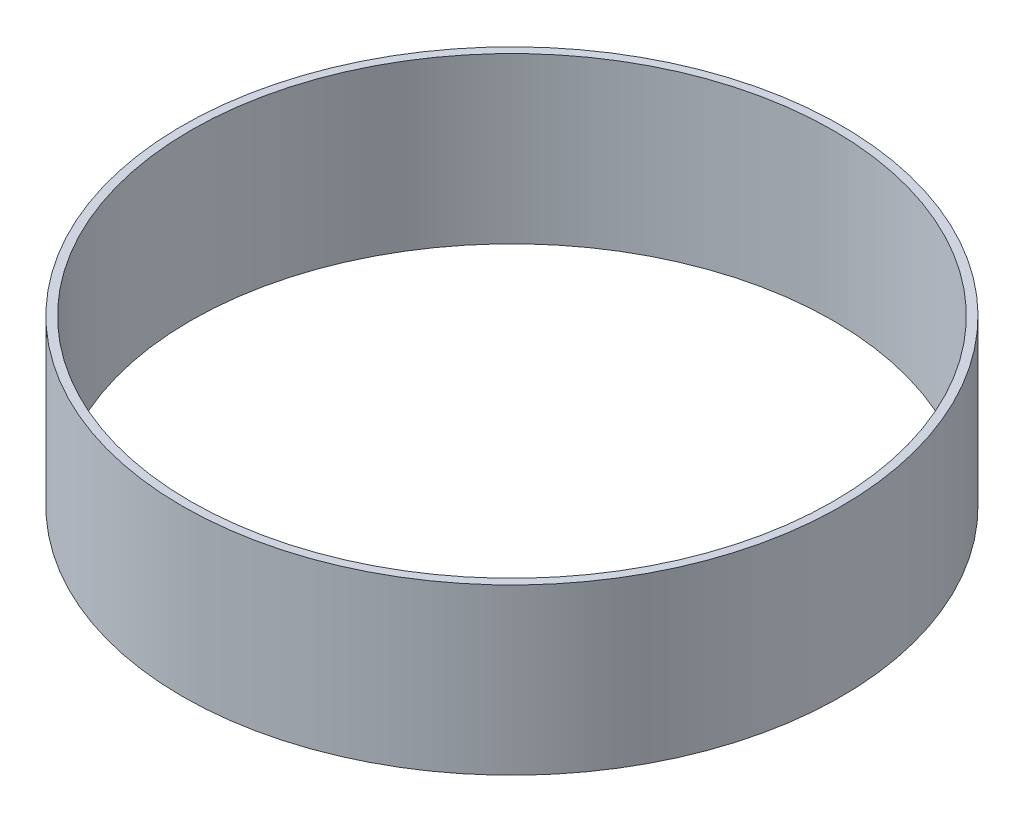
SolidWorks part; units mm, degrees
material "Wildman Fiberglass"
ref_plane "Front Plane" through (0, 0, 0) normal (0, 0, 1) x (1, 0, 0)
ref_plane "Top Plane" through (0, 0, 0) normal (0, 1, 0) x (1, 0, 0)
ref_plane "Right Plane" through (0, 0, 0) normal (1, 0, 0) x (0, 0, -1)
sketch "Sketch1" plane through (0, 0, 0) normal (0, 1, 0) x (1, 0, 0)
  circle A0 centre (0, 0) radius 49.53
  circle A1 centre (0, 0) radius 50.8
  dimension "D1" = 101.6
  dimension "D2" = 99.06
extrude "Boss-Extrude1" add sketch "Sketch1" along normal blind 25.4
equation "\"Length\"=1"
equation "\"D1@Boss-Extrude1\"=\"Length\""
